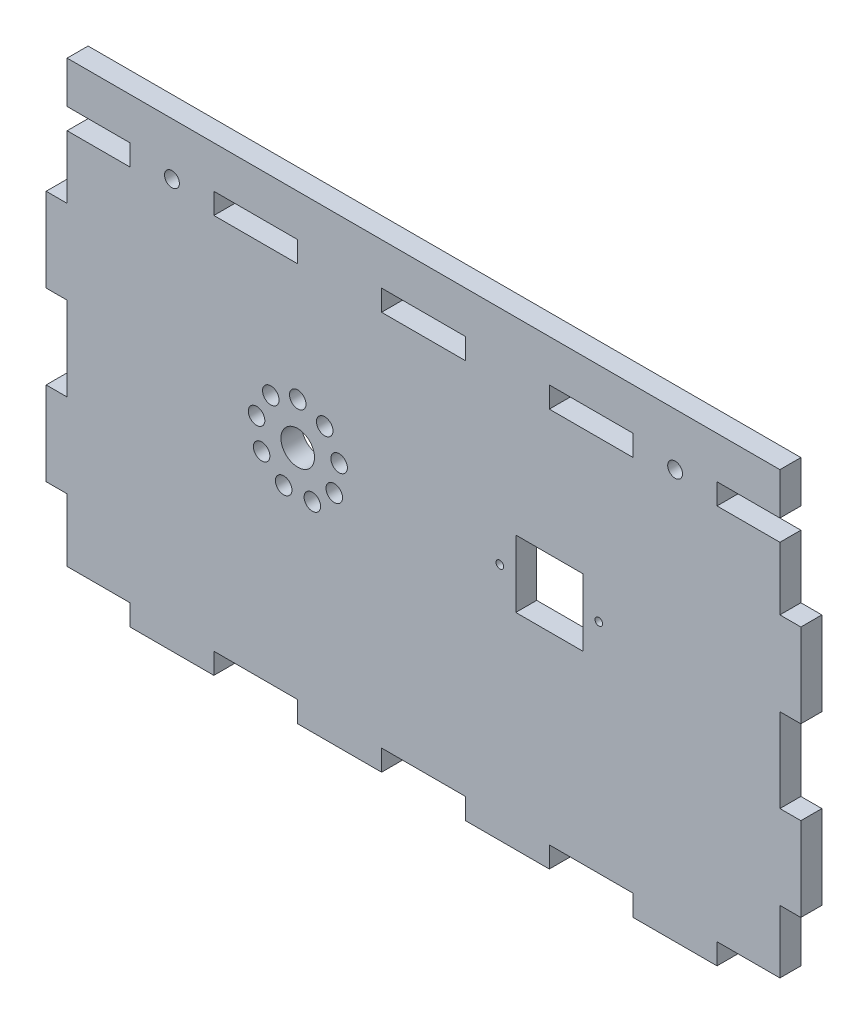
SolidWorks part; units mm, degrees
ref_plane "Front Plane" through (0, 0, 0) normal (0, 0, 1) x (1, 0, 0)
ref_plane "Top Plane" through (0, 0, 0) normal (0, 1, 0) x (1, 0, 0)
ref_plane "Right Plane" through (0, 0, 0) normal (1, 0, 0) x (0, 0, -1)
sketch "Sketch1" plane through (0, 0, 0) normal (0, 0, 1) x (1, 0, 0)
  line L1 (0, 0) -> (228.6, 0)
  line L2 (0, 0) -> (0, 139.7)
  line L3 (0, 139.7) -> (228.6, 139.7)
  line L4 (228.6, 0) -> (228.6, 139.7)
  dimension "D1" = 228.6
  dimension "D2" = 139.7
extrude "Boss-Extrude1" add sketch "Sketch1" along normal blind 6.35
sketch "Sketch5" plane through (0, 0, 6.35) normal (0, 0, 1) x (1, 0, 0)
  line L1 (0, 0) -> (6.35, 0)
  line L2 (0, 0) -> (0, 25.4)
  line L3 (0, 25.4) -> (6.35, 25.4)
  line L4 (6.35, 0) -> (6.35, 25.4)
  dimension "D1" = 25.4
  dimension "D2" = 6.35
extrude "Cut-Extrude4" cut sketch "Sketch5" against normal blind 6.35
sketch "Sketch6" plane through (0, 0, 6.35) normal (0, 0, 1) x (1, 0, 0)
  line L1 (0, 0) -> (25.4, 0)
  line L2 (0, 0) -> (0, 6.35)
  line L3 (0, 6.35) -> (25.4, 6.35)
  line L4 (25.4, 0) -> (25.4, 6.35)
  dimension "D1" = 6.35
  dimension "D2" = 25.4
extrude "Cut-Extrude5" cut sketch "Sketch6" against normal blind 6.35
pattern_linear "LPattern5" count 3 spacing 50.8 along (0, 1, 0) count 2 spacing 222.25 along (1, 0, 0) of "Cut-Extrude4"
pattern_linear "LPattern6" count 5 spacing 50.8 along (1, 0, 0) count 2 spacing 120.65 along (0, 1, 0) of "Cut-Extrude5"
sketch "Sketch7" plane through (0, 0, 6.35) normal (0, 0, 1) x (1, 0, 0)
  line L1 (6.35, 120.65) -> (0, 120.65)
  line L2 (6.35, 120.65) -> (6.35, 139.7)
  line L3 (6.35, 139.7) -> (0, 139.7)
  line L4 (0, 120.65) -> (0, 139.7)
  dimension "D1" = 6.35
  dimension "D2" = 19.05
extrude "Cut-Extrude6" cut sketch "Sketch7" against normal blind 6.35
sketch "Sketch8" plane through (0, 0, 6.35) normal (0, 0, 1) x (1, 0, 0)
  line L1 (228.6, 139.7) -> (222.25, 139.7)
  line L2 (228.6, 139.7) -> (228.6, 120.65)
  line L3 (228.6, 120.65) -> (222.25, 120.65)
  line L4 (222.25, 139.7) -> (222.25, 120.65)
extrude "Cut-Extrude7" cut sketch "Sketch8" against normal blind 6.35
hole_wizard "#8 Clearance Hole1" positions "Sketch10" profile "Sketch9" hole size "#8" standard "ANSI Inch"
sketch "Sketch10" plane through (0, 0, 6.35) normal (0, 0, 1) x (1, 0, 0)
  line L0 (203.2, 127) -> (203.2, 120.65) construction
  line L1 (222.25, 127) -> (203.2, 127) construction
  line L2 (25.4, 120.65) -> (25.4, 127) construction
  line L3 (76.2, 127) -> (50.8, 127) construction
  point P0 (38.1, 123.825)
  point P2 (190.5, 123.825)
  point P7 (203.2, 123.825)
  point P10 (25.4, 123.825)
  dimension "D1" = 12.7
  dimension "D2" = 3.175
  dimension "D3" = 12.7
  dimension "D4" = 3.175
sketch "Sketch9" plane through (38.1, 123.825, 6.35) normal (1, 0, 0) x (0, -1, 0)
  line L0 (0, 0) -> (0, 11.5107)
  line L1 (0, 11.5107) -> (2.2479, 10.16)
  line L2 (2.2479, 10.16) -> (2.2479, 0)
  line L5 (2.2479, 0) -> (0, 0)
  line L10 (0, 11.5107) -> (-2.2479, 10.16) construction
  line L11 (0, -6.35) -> (0, 107.95) construction
  dimension "Hole Dia." = 4.4958
  dimension "Hole Depth" = 10.16
  dimension "Drill Angle" = 118
sketch "Sketch11" plane through (0, 0, 6.35) normal (0, 0, 1) x (1, 0, 0)
  line L0 (101.6, 120.65) -> (127, 120.65) construction
  line L1 (142.24, 82.55) -> (162.56, 82.55)
  line L2 (142.24, 82.55) -> (142.24, 62.23)
  line L3 (142.24, 62.23) -> (162.56, 62.23)
  line L4 (162.56, 82.55) -> (162.56, 62.23)
  line L6 (0, 101.6) -> (0, 76.2) construction
  circle A0 centre (137.414, 72.39) radius 1.143
  circle A1 centre (167.386, 72.39) radius 1.143
  point P6 (152.4, 82.55)
  point P13 (162.56, 72.39)
  point P14 (142.24, 72.39)
  dimension "D5" = 2.286
  dimension "D6" = 2.286
  dimension "D7" = 14.986
  dimension "D8" = 14.986
  dimension "D1" = 38.1
  dimension "D2" = 20.32
  dimension "D3" = 20.32
  dimension "D4" = 152.4
extrude "Cut-Extrude8" cut sketch "Sketch11" against normal blind 7.62
sketch "Sketch12" plane through (0, 0, 6.35) normal (0, 0, 1) x (1, 0, 0)
  line L0 (0, 101.6) -> (0, 76.2) construction
  circle A0 centre (76.2, 72.39) radius 5.08
  dimension "D1" = 10.16
  dimension "D2" = 76.2
extrude "Cut-Extrude9" cut sketch "Sketch12" against normal blind 7.62
sketch "Sketch13" plane through (0, 0, 6.35) normal (0, 0, 1) x (1, 0, 0)
  circle A0 centre (76.2, 85.09) radius 2.5
  circle A1 centre (84.3739, 82.1477) radius 2.5
  circle A2 centre (88.7442, 74.6396) radius 2.5
  circle A3 centre (87.266, 66.079) radius 2.5
  circle A4 centre (80.6309, 60.4713) radius 2.5
  circle A5 centre (71.9436, 60.4405) radius 2.5
  circle A6 centre (65.2689, 66.001) radius 2.5
  circle A7 centre (63.7301, 74.551) radius 2.5
  circle A8 centre (68.0471, 82.0899) radius 2.5
  circle A9 centre (76.2, 72.39) radius 5.08 construction
  point P20 (76.245, 72.39)
  dimension "D1" = 5
  dimension "D3" = 12.7
  dimension "D4" = 0
  dimension "D2" = 9
extrude "Cut-Extrude10" cut sketch "Sketch13" against normal blind 7.62
